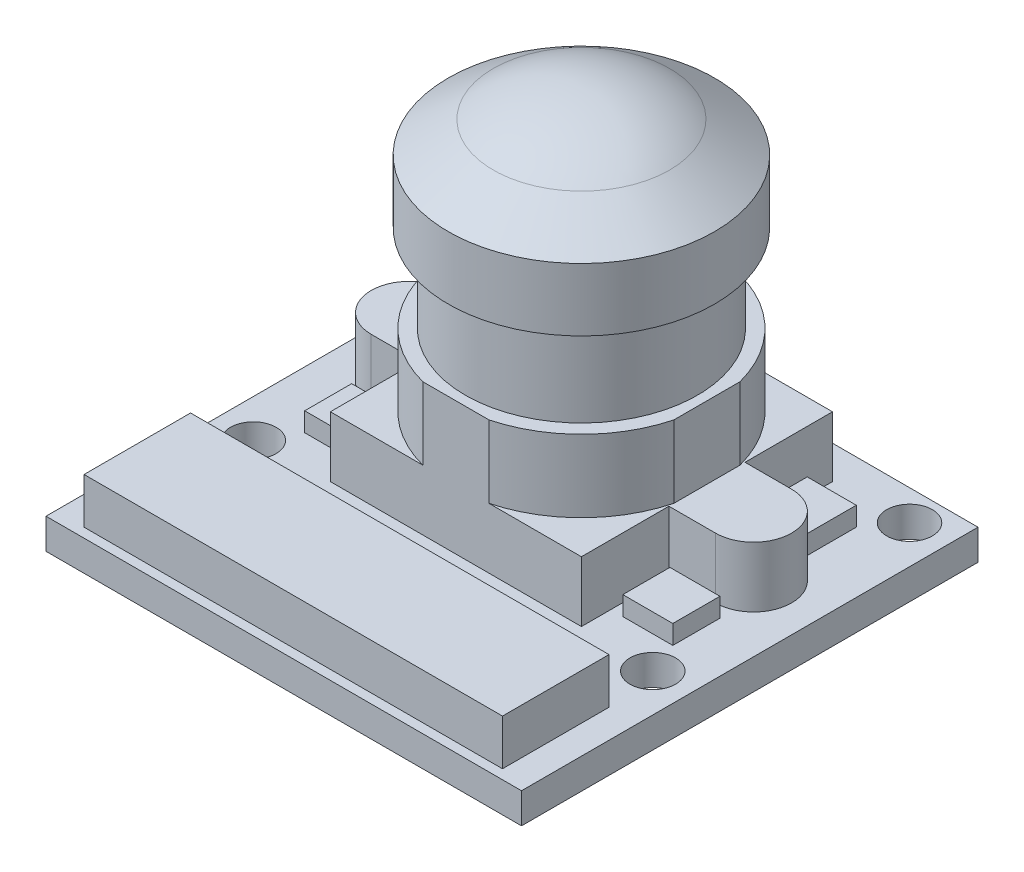
SolidWorks part; units mm, degrees
ref_plane "Plan de face" through (0, 0, 0) normal (0, 0, 1) x (1, 0, 0)
ref_plane "Plan de dessus" through (0, 0, 0) normal (0, 1, 0) x (1, 0, 0)
ref_plane "Plan de droite" through (0, 0, 0) normal (1, 0, 0) x (0, 0, -1)
sketch "Esquisse1" plane through (0, 0, 0) normal (0, 1, 0) x (1, 0, 0)
  line L0 (-12.5, -12) -> (12.5, 12) construction
  line L1 (-12.5, 12) -> (12.5, 12)
  line L2 (-12.5, 12) -> (-12.5, -12)
  line L3 (-12.5, -12) -> (12.5, -12)
  line L4 (12.5, 12) -> (12.5, -12)
  point P4 (0, 0)
  dimension "D1" = 24
  dimension "D2" = 25
extrude "Boss.-Extru.1" add sketch "Esquisse1" along normal blind 1.6
sketch "Esquisse4" plane through (0, 1.6, 0) normal (0, 1, 0) x (1, 0, 0)
  line L7 (6.6, 10.25) -> (6.6, 5.65)
  line L8 (9.05, 1.65) -> (6.6, 1.65)
  line L9 (9.05, 5.65) -> (6.6, 5.65)
  line L10 (6.6, 1.65) -> (6.6, -2.95)
  line L14 (0, -2.95) -> (0, 10.25) construction
  line L15 (-6.6, -2.95) -> (6.6, -2.95)
  line L16 (6.6, 10.25) -> (-6.6, 10.25)
  line L17 (-6.6, 1.65) -> (-6.6, -2.95)
  line L18 (-9.05, 5.65) -> (-6.6, 5.65)
  line L19 (-9.05, 1.65) -> (-6.6, 1.65)
  line L20 (-6.6, 10.25) -> (-6.6, 5.65)
  line L21 (-12.5, -12) -> (12.5, -12) construction
  arc A0 (9.05, 1.65) -> (9.05, 5.65) centre (9.05, 3.65) ccw
  arc A2 (-9.05, 1.65) -> (-9.05, 5.65) centre (-9.05, 3.65) cw
  point P16 (0, 3.65)
  point P21 (11.05, 3.65)
  dimension "D4" = 2
  dimension "D1" = 15.65
  dimension "D2" = 13.2
  dimension "D3" = 4.45
extrude "Boss.-Extru.2" add sketch "Esquisse4" along normal blind 3.18
sketch "Esquisse5" plane through (0, 4.78, 0) normal (0, 1, 0) x (1, 0, 0)
  line L0 (-6.6, 10.25) -> (6.6, -2.95) construction
  line L1 (-6.6, 1.912) -> (-6.6, 5.388)
  line L7 (-1.738, -2.95) -> (1.738, -2.95)
  line L8 (-6.6, -2.95) -> (6.6, -2.95) construction
  line L9 (0, 3.65) -> (0, 5.7992) construction
  line L10 (0, 3.65) -> (1.4511, 3.65) construction
  line L11 (-1.738, 10.25) -> (1.738, 10.25)
  line L12 (6.6, 1.912) -> (6.6, 5.388)
  arc A4 (-6.6, 1.912) -> (-1.738, -2.95) centre (0, 3.65) ccw
  arc A5 (-6.6, 5.388) -> (-1.738, 10.25) centre (0, 3.65) cw
  arc A6 (6.6, 1.912) -> (1.738, -2.95) centre (0, 3.65) cw
  arc A7 (6.6, 5.388) -> (1.738, 10.25) centre (0, 3.65) ccw
  point P10 (0, 10.25)
  point P24 (-6.6, 3.65)
  point P28 (0, -2.95)
  dimension "D1" = 6.825
extrude "Boss.-Extru.3" add sketch "Esquisse5" along normal blind 3.8
sketch "Esquisse6" plane through (0, 8.58, 0) normal (0, 1, 0) x (1, 0, 0)
  circle A0 centre (0, 3.65) radius 6.1
  dimension "D1" = 12.2
extrude "Boss.-Extru.4" add sketch "Esquisse6" along normal blind 4.6
ref_plane "Plan1" through (0, 0, -3.65) normal (0, 0, -1) x (-1, 0, 0)
sketch "Esquisse8" plane through (0, 0, -3.65) normal (0, 0, 1) x (1, 0, 0)
  line L0 (0, 13.18) -> (-7, 13.18)
  line L1 (6.1, 13.18) -> (-6.1, 13.18) construction
  line L2 (-7, 13.18) -> (-7, 16.48)
  line L3 (-7, 16.48) -> (-4.6317, 18.0985)
  line L4 (0, 13.18) -> (0, 19.53)
  arc A0 (-4.6317, 18.0985) -> (0, 19.53) centre (0, 11.3211) cw
  dimension "D1" = 7
  dimension "D2" = 3.3
  dimension "D3" = 6.35
revolve "Révolution1" add sketch "Esquisse8" angle 360 about L4
hole_wizard "Dégagement M21" positions "Esquisse9" profile "Esquisse10" hole size "M2" standard "Ansi Metric" end condition through all
sketch "Esquisse9" plane through (0, 1.6, 0) normal (0, 1, 0) x (1, 0, 0)
  line L0 (0, 3.65) -> (0, 5.9159) construction
  line L2 (0, 3.65) -> (2.1745, 3.65) construction
  point P0 (-10.5, 10.4)
  point P15 (10.5, 10.4)
  point P16 (10.5, -3.1)
  point P17 (-10.5, -3.1)
  dimension "D1" = 21
  dimension "D2" = 13.5
sketch "Esquisse10" plane through (-10.5, 1.6, -10.4) normal (1, 0, 0) x (0, 0, 1)
  line L0 (0, 0) -> (0, 1.6)
  line L1 (0, 1.6) -> (1.2, 1.6)
  line L2 (1.2, 1.6) -> (1.2, 0)
  line L5 (1.2, 0) -> (0, 0)
  line L11 (0, -6.35) -> (0, 107.95) construction
  dimension "Diamètre du perçage jusqu'au prochain" = 2.4
  dimension "Profondeur du perçage jusqu'au prochain" = 1.6
sketch "Esquisse11" plane through (0, 1.6, 0) normal (0, 1, 0) x (1, 0, 0)
  line L0 (-12.5, -12) -> (12.5, -12) construction
  line L1 (-11, -5.9) -> (11, -5.9)
  line L2 (-11, -5.9) -> (-11, -11.5)
  line L3 (-11, -11.5) -> (11, -11.5)
  line L4 (11, -5.9) -> (11, -11.5)
  point P4 (0, -11.5)
  dimension "D1" = 22
  dimension "D2" = 5.6
  dimension "D3" = 0.5
extrude "Boss.-Extru.6" add sketch "Esquisse11" along normal blind 2.4
sketch "Esquisse12" plane through (0, 0, 0) normal (0, -1, 0) x (1, 0, 0)
  circle A0 centre (-9.05, -3.65) radius 1.56
  circle A1 centre (9.05, -3.65) radius 1.56
  dimension "D1" = 3.12
extrude "Boss.-Extru.7" add sketch "Esquisse12" along normal blind 1.1
sketch "Esquisse13" plane through (0, 1.6, 0) normal (0, 1, 0) x (1, 0, 0)
  line L0 (12.5, 12) -> (-12.5, 12) construction
  line L1 (6.7228, 8.8) -> (9.3, 8.8)
  line L2 (6.7228, 8.8) -> (6.7228, 5.7794)
  line L3 (6.7228, 5.7794) -> (9.3, 5.7794)
  line L4 (9.3, 8.8) -> (9.3, 5.7794)
  line L5 (12.5, -12) -> (12.5, 12) construction
  line L6 (-12.5, 12) -> (-12.5, -12) construction
  line L7 (7.2328, 1.0707) -> (9.8609, 1.0707)
  line L8 (7.2328, 1.0707) -> (7.2328, -1.4069)
  line L9 (7.2328, -1.4069) -> (9.8609, -1.4069)
  line L10 (9.8609, 1.0707) -> (9.8609, -1.4069)
  line L11 (-9.5, 1.0707) -> (-7.2399, 1.0707)
  line L12 (-9.5, 1.0707) -> (-9.5, -1.4)
  line L13 (-9.5, -1.4) -> (-7.2399, -1.4)
  line L14 (-7.2399, 1.0707) -> (-7.2399, -1.4)
  line L15 (-9.7, 8.2) -> (-6.949, 8.2)
  line L16 (-9.7, 8.2) -> (-9.7, 5.8854)
  line L17 (-9.7, 5.8854) -> (-6.949, 5.8854)
  line L18 (-6.949, 8.2) -> (-6.949, 5.8854)
  line L19 (-12.5, -12) -> (12.5, -12) construction
  dimension "D1" = 3.2
  dimension "D2" = 3.2
  dimension "D3" = 3.8
  dimension "D4" = 2.8
  dimension "D5" = 3
  dimension "D6" = 10.6
extrude "Boss.-Extru.8" add sketch "Esquisse13" along normal blind 1
ref_point "camera origin"
ref_axis "Axe1" through (0, -2.1315, -3.65) along (0, 1, 0)
ref_plane "Plan2" through (0, 2000, 0) normal (0, 1, 0) x (1, 0, 0)
ref_point "camera target"
equation "\"D2@Esquisse13\"=\"D1@Esquisse13\""
